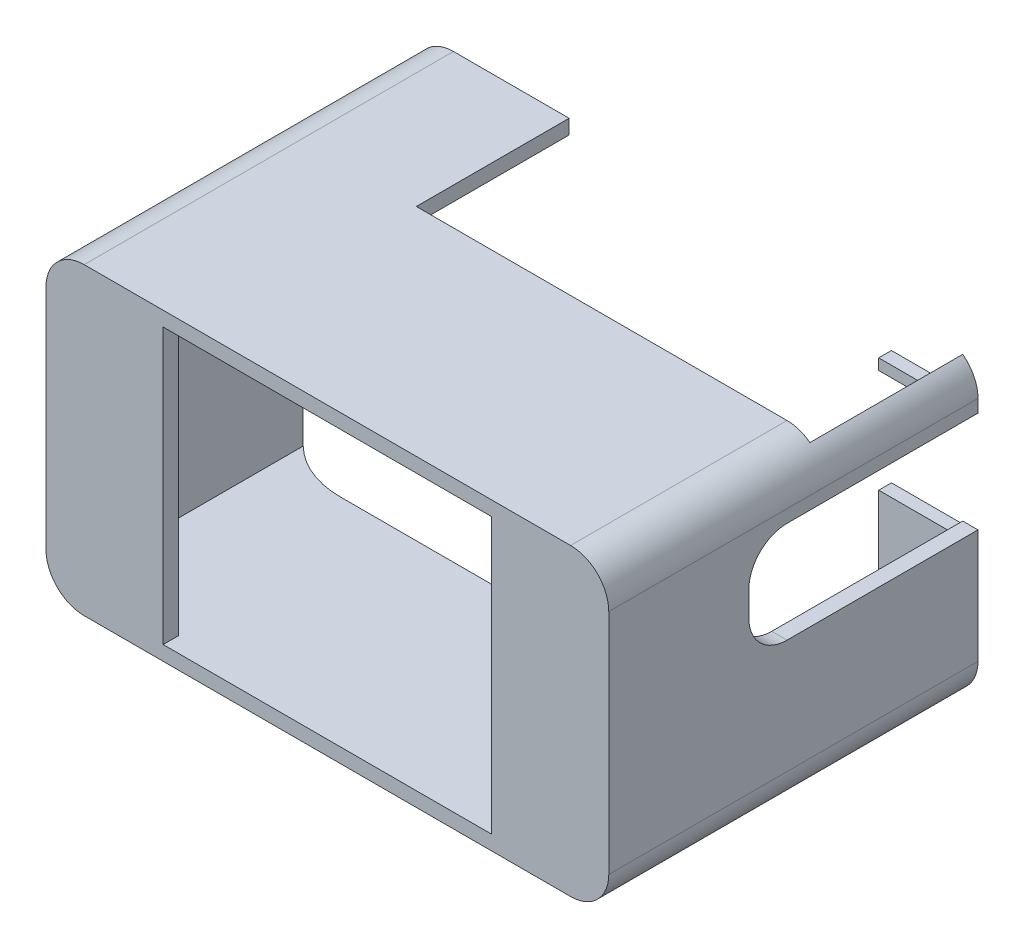
SolidWorks part; units mm, degrees
ref_plane "前视基准面" through (0, 0, 0) normal (0, 0, 1) x (1, 0, 0)
ref_plane "上视基准面" through (0, 0, 0) normal (0, 1, 0) x (1, 0, 0)
ref_plane "右视基准面" through (0, 0, 0) normal (1, 0, 0) x (0, 0, -1)
other "Configuration Table"
sketch "草图1" plane through (0, 0, 0) normal (0, 0, 1) x (1, 0, 0)
  line L0 (98, 34) -> (89, 34) construction
  line L1 (87, -1) -> (115, -1)
  line L2 (87, -1) -> (87, -44)
  line L3 (87, -44) -> (115, -44)
  line L4 (115, -1) -> (115, -44)
  line L5 (87, 44) -> (115, 44)
  line L6 (87, 44) -> (87, 34)
  line L7 (87, 34) -> (115, 34)
  line L8 (115, 44) -> (115, 34)
  line L10 (115, 44) -> (115, -44)
  line L13 (87, 36) -> (87, 44) construction
  line L14 (89, -1) -> (98, -1) construction
  line L15 (87, -44) -> (87, -3) construction
  line L16 (87, -44) -> (100, -44) construction
  line L17 (100, 44) -> (87, 44) construction
  line L18 (115, 59.7) -> (121, 59.7)
  line L19 (115, 59.7) -> (115, -59.7)
  line L20 (115, -59.7) -> (121, -59.7)
  line L21 (121, 59.7) -> (121, -59.7)
  line L23 (-29.57, -59.7) -> (90, -59.7) construction
  line L24 (-29.57, 59.7) -> (90, 59.7) construction
  dimension "D1" = 28
  dimension "D2" = 6
extrude "凸台-拉伸1" add sketch "草图1" along normal blind 5 contours L8 L5 L6 L7 | L4 L1 L2 L3 | L21 L18 L19 L8 L10 L4 L20 region at (101, -22.5, 0) region at (118, 0, 0) region at (101, 39, 0)
sketch "草图2" plane through (0, 0, 5) normal (0, 0, 1) x (1, 0, 0)
  line L0 (115, 44) -> (115, 34)
  line L1 (115, -1) -> (115, -44)
  line L12 (87, 34) -> (115, 34)
  line L13 (115, 34) -> (115, -1)
  line L14 (115, -1) -> (87, -1)
  line L15 (87, -1) -> (87, -44)
  line L16 (87, -44) -> (115, -44)
  line L17 (115, -44) -> (115, -59.7)
  line L18 (115, -59.7) -> (121, -59.7)
  line L19 (121, -59.7) -> (121, 59.7)
  line L20 (121, 59.7) -> (115, 59.7)
  line L21 (115, 59.7) -> (115, 44)
  line L22 (115, 44) -> (87, 44)
  line L23 (87, 44) -> (87, 34)
  line L25 (115, 34) -> (115, -1)
  line L29 (115, -44) -> (115, -59.7)
  line L30 (115, -59.7) -> (121, -59.7)
  line L31 (121, -59.7) -> (121, 59.7)
  line L32 (121, 59.7) -> (115, 59.7)
  line L33 (115, 59.7) -> (115, 44)
  dimension "D1" = 0
extrude "凸台-拉伸2" add sketch "草图2" along normal blind 140
sketch "草图3" plane through (115, 0, 0) normal (-1, 0, 0) x (0, 0, 1)
  line L0 (145, -59.7) -> (0, -59.7) construction
  line L1 (145, 59.7) -> (139, 59.7)
  line L2 (145, 59.7) -> (145, -59.7)
  line L3 (145, -59.7) -> (139, -59.7)
  line L4 (139, 59.7) -> (139, -59.7)
  dimension "D1" = 6
extrude "凸台-拉伸3" add sketch "草图3" along normal up to surface (215 mm away)
ref_plane "基准面1" through (0, 0, 0) normal (0, 1, 0) x (1, 0, 0)
sketch "草图6" plane through (0, 0, 139) normal (0, 0, -1) x (-1, 0, 0)
  line L0 (100, 59.7) -> (-115, 59.7) construction
  line L1 (100, -59.7) -> (94, -59.7)
  line L2 (100, -59.7) -> (100, 59.7)
  line L3 (100, 59.7) -> (94, 59.7)
  line L4 (94, -59.7) -> (94, 59.7)
  dimension "D1" = 6
extrude "凸台-拉伸5" add sketch "草图6" along normal up to surface (139 mm away)
sketch "草图7" plane through (-100, 0, 0) normal (-1, 0, 0) x (0, 0, 1)
  line L1 (0, -59.7) -> (50, -59.7)
  line L2 (0, -59.7) -> (0, 0)
  line L3 (0, 0) -> (50, 0)
  line L4 (50, -59.7) -> (50, 0)
  dimension "D1" = 50
extrude "切除-拉伸1" cut sketch "草图7" against normal up to surface (6 mm away) up to face at (-94, 0, 69.5)
sketch "草图8" plane through (-100, 0, 0) normal (-1, 0, 0) x (0, 0, 1)
  line L1 (0, 59.7) -> (65, 59.7)
  line L2 (0, 59.7) -> (0, 54)
  line L3 (0, 54) -> (65, 54)
  line L4 (65, 59.7) -> (65, 54)
  dimension "D1" = 65
  dimension "D2" = 5.7
extrude "凸台-拉伸6" add sketch "草图8" against normal up to surface (60.43 mm away)
sketch "草图9" plane through (0, 0, 145) normal (0, 0, 1) x (1, 0, 0)
  line L0 (121, -59.7) -> (121, 59.7) construction
  line L1 (-100, 59.7) -> (121, 59.7)
  line L2 (-100, 59.7) -> (-100, 54)
  line L3 (-100, 54) -> (121, 54)
  line L4 (121, 59.7) -> (121, 54)
  line L5 (-100, 59.7) -> (-100, -59.7) construction
  line L6 (121, -59.7) -> (-100, -59.7)
  line L7 (121, -59.7) -> (121, -54)
  line L8 (121, -54) -> (-100, -54)
  line L9 (-100, -59.7) -> (-100, -54)
  dimension "D1" = 5.7
  dimension "D2" = 5.7
extrude "凸台-拉伸7" add sketch "草图9" against normal up to surface (85 mm away)
sketch "草图10" plane through (0, 0, 139) normal (0, 0, -1) x (-1, 0, 0)
  line L0 (94, 54) -> (-115, 54) construction
  line L1 (-75, 54) -> (54, 54)
  line L2 (-75, 54) -> (-75, -54)
  line L3 (-75, -54) -> (54, -54)
  line L4 (54, 54) -> (54, -54)
  line L5 (94, -54) -> (-115, -54) construction
  line L6 (94, 54) -> (94, 0) construction
  line L7 (-115, 54) -> (-115, -54) construction
  dimension "D1" = 40
  dimension "D2" = 40
extrude "切除-拉伸2" cut sketch "草图10" against normal through all
sketch "草图14" plane through (121, 0, 0) normal (1, 0, 0) x (0, 0, -1)
  line L0 (-145, 59.7) -> (0, 59.7) construction
  line L1 (0, 0) -> (-90, 0)
  line L2 (0, 0) -> (0, 39.7)
  line L3 (0, 39.7) -> (-90, 39.7)
  line L4 (-90, 0) -> (-90, 39.7)
  line L5 (-145, -59.7) -> (-145, 59.7) construction
  dimension "D1" = 20
  dimension "D2" = 55
extrude "切除-拉伸3" cut sketch "草图14" against normal up to next
fillet "圆角2" radius 15 4 edges at (-100, 59.7, 72.5) (121, 59.7, 72.5) (-100, -59.7, 97.5) (121, -59.7, 72.5)
fillet "圆角3" radius 15 2 edges at (-97, 0, 0) (-97, 0, 50)
fillet "圆角4" radius 15 2 edges at (118, 39.7, 90) (118, 0, 90)
fillet "圆角5" radius 35 1 edges at (-94, -55.35, 60)
